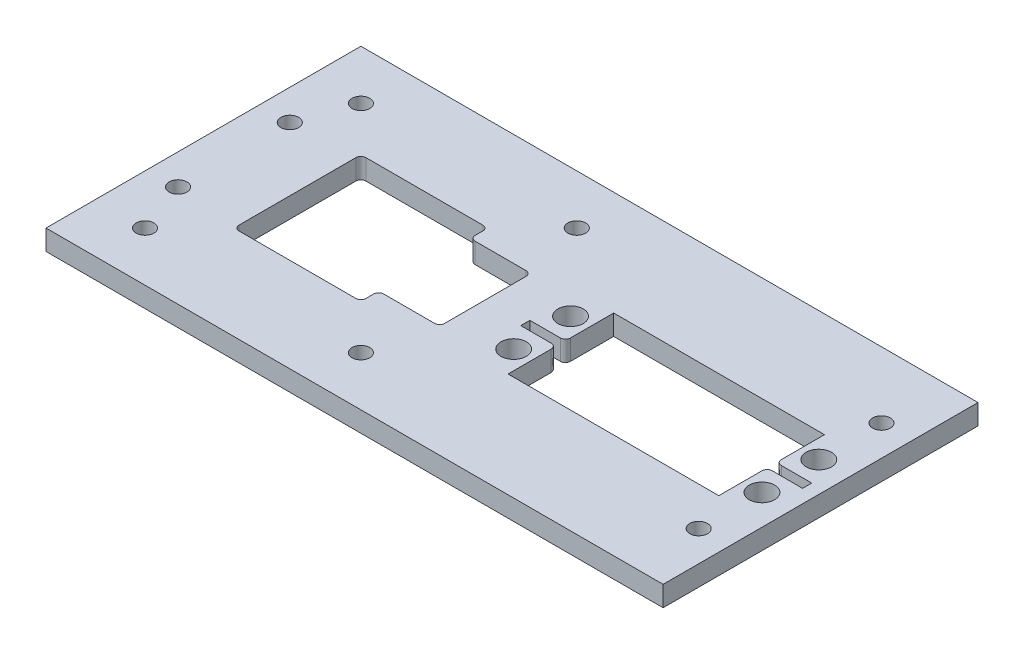
SolidWorks part; units mm, degrees
material "PLA"
ref_plane "Front Plane" through (0, 0, 0) normal (0, 0, 1) x (1, 0, 0)
ref_plane "Top Plane" through (0, 0, 0) normal (0, 1, 0) x (1, 0, 0)
ref_plane "Right Plane" through (0, 0, 0) normal (1, 0, 0) x (0, 0, -1)
sketch "Sketch1" plane through (0, 0, 0) normal (0, 1, 0) x (1, 0, 0)
  line L0 (-37, 17.5) -> (-2, 17.5) construction
  line L1 (-50.5, 31) -> (71, 31)
  line L2 (-50.5, 31) -> (-50.5, -31)
  line L3 (-50.5, -31) -> (71, -31)
  line L4 (71, 31) -> (71, -31)
  line L7 (-32, 12.5) -> (-7, 12.5)
  line L8 (-32, 12.5) -> (-32, -12.5)
  line L9 (-32, -12.5) -> (-7, -12.5)
  line L10 (-7, 12.5) -> (-7, -12.5)
  line L11 (-2, 17.5) -> (-2, -17.5) construction
  line L12 (-37, -17.5) -> (-2, -17.5) construction
  line L13 (-37, 17.5) -> (-37, -17.5) construction
  line L14 (5.5, 25) -> (5.5, -25) construction
  line L15 (-44.5, -25) -> (5.5, -25) construction
  line L16 (-44.5, 25) -> (-44.5, -25) construction
  line L17 (-44.5, 25) -> (5.5, 25) construction
  line L18 (-32, 0) -> (-7, 0) construction
  circle A0 centre (0, 0) radius 6 construction
  circle A1 centre (0, 0) radius 12.5 construction
  circle A2 centre (32.5, 0) radius 20 construction
  circle A3 centre (-19.5, 0) radius 8.5 construction
  circle A4 centre (-19.5, 0) radius 3.175 construction
  dimension "D1" = 12
  dimension "D8" = 25
  dimension "D9" = 40
  dimension "D13" = 17
  dimension "D14" = 6.35
  dimension "D2" = 25
  dimension "D3" = 25
  dimension "D12" = 71
  dimension "D7" = 19.5
  dimension "D11" = 6
  dimension "D6" = 6
  dimension "D10" = 6
  dimension "D4" = 5
  dimension "D5" = 7.5
extrude "Boss-Extrude1" add sketch "Sketch1" along normal blind 4
sketch "Sketch2" plane through (0, 4, 0) normal (0, 1, 0) x (1, 0, 0)
  line L0 (19.87, -0.9) -> (12.87, -0.9)
  line L11 (12.87, -0.9) -> (12.87, 0.9)
  line L24 (12.87, 0.9) -> (19.87, 0.9)
  line L29 (19.87, 0.9) -> (19.87, 10.4)
  line L47 (60.97, 0.5) -> (67.97, 0.5) construction
  line L48 (67.97, 0.5) -> (67.97, -0.5) construction
  line L55 (60.97, -0.5) -> (67.97, -0.5) construction
  line L65 (13.27, 0.5) -> (20.27, 0.5) construction
  line L68 (13.27, -0.5) -> (13.27, 0.5) construction
  line L71 (13.27, -0.5) -> (20.27, -0.5) construction
  line L76 (20.27, 10) -> (60.97, 10) construction
  line L77 (60.97, 10) -> (60.97, 0.5) construction
  line L78 (60.97, -10) -> (20.27, -10) construction
  line L79 (20.27, -10) -> (20.27, -0.5) construction
  line L80 (60.97, -0.5) -> (60.97, -10) construction
  line L81 (20.27, 0.5) -> (20.27, 10) construction
  line L82 (19.87, 10.4) -> (61.37, 10.4)
  line L83 (61.37, 10.4) -> (61.37, 0.9)
  line L84 (61.37, 0.9) -> (68.37, 0.9)
  line L85 (68.37, 0.9) -> (68.37, -0.9)
  line L86 (68.37, -0.9) -> (61.37, -0.9)
  line L87 (61.37, -0.9) -> (61.37, -10.4)
  line L88 (61.37, -10.4) -> (19.87, -10.4)
  line L89 (19.87, -10.4) -> (19.87, -0.9)
  circle A4 centre (65.06, 5.6) radius 2.1 construction
  circle A5 centre (65.06, -5.6) radius 2.1 construction
  circle A6 centre (16.18, 5.6) radius 2.1 construction
  circle A7 centre (16.18, -5.6) radius 2.1 construction
  circle A8 centre (16.18, 5.6) radius 2.5
  circle A9 centre (16.18, -5.6) radius 2.5
  circle A10 centre (65.06, -5.6) radius 2.5
  circle A11 centre (65.06, 5.6) radius 2.5
extrude "Cut-Extrude1" cut sketch "Sketch2" against normal through all contours L24 L29 L82 L83 L84 L85 L86 L87 L88 L89 L0 L11 | A8 | A9 | A11 | A10
ref_axis "Axis2" through (0, 0, 0) along (0, 1, 0)
sketch "Sketch3" plane through (0, 4, 0) normal (0, 1, 0) x (1, 0, 0)
  line L0 (71, 31) -> (-50.5, 31) construction
  line L1 (-50.5, 31) -> (-50.5, -31) construction
  line L2 (-50.5, -31) -> (71, -31) construction
  line L3 (71, -31) -> (71, 31) construction
  circle A5 centre (1.75, 21.25) radius 1.75
  circle A6 centre (1.75, -21.25) radius 1.75
  circle A7 centre (-40.75, -21.25) radius 1.75
  circle A8 centre (-40.75, 21.25) radius 1.75
  circle A9 centre (-44.5, 11) radius 1.75
  circle A10 centre (-44.5, -11) radius 1.75
  circle A11 centre (65, -18) radius 1.75
  circle A12 centre (65, 18) radius 1.75
  dimension "D6" = 6
  dimension "D1" = 3.5
  dimension "D2" = 20
  dimension "D3" = 6
  dimension "D4" = 20
  dimension "D5" = 13
  dimension "D7" = 13
extrude "Cut-Extrude2" cut sketch "Sketch3" against normal through all contours A7 | A10 | A6 | A5 | A12 | A11 | A9 | A8 region at (1.75, 4, -21.25) region at (1.75, 4, 21.25) region at (-40.75, 4, 21.25) region at (-44.5, 4, 11) region at (65, 4, 18) region at (65, 4, -18)
sketch "Sketch4" plane through (0, 4, 0) normal (0, 1, 0) x (1, 0, 0)
  line L0 (-50.5, 0) -> (71, 0) construction
  line L1 (-50.5, 31) -> (-50.5, -31) construction
  line L2 (71, -31) -> (71, 31) construction
  line L3 (-7, -12.5) -> (-7, 12.5) construction
  line L4 (-7, 9) -> (5, 9)
  line L5 (-7, 9) -> (-7, -9)
  line L6 (-7, -9) -> (5, -9)
  line L7 (5, 9) -> (5, -9)
  dimension "D1" = 18
  dimension "D2" = 12
extrude "Cut-Extrude3" cut sketch "Sketch4" against normal through all
fillet "Fillet1" radius 1 12 edges at (-7, 2, -9) (-7, 2, -12.5) (-32, 2, 12.5) (-7, 2, 12.5) (-7, 2, 9) (5, 2, 9) (5, 2, -9) (-32, 2, -12.5) (61.37, 2, 0.9) (61.37, 2, -0.9) (19.87, 2, 0.9) (19.87, 2, -0.9)
equation "\"D6@Sketch1\"=\"D11@Sketch1\""
equation "\"D10@Sketch1\"=\"D11@Sketch1\""
equation "\"D4@Sketch3\"=\"D2@Sketch3\""
